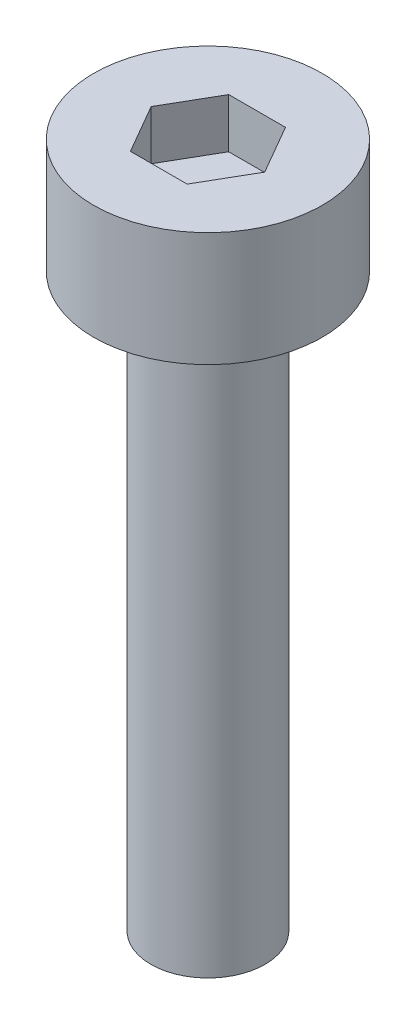
SolidWorks part; units mm, degrees
ref_plane "Front Plane" through (0, 0, 0) normal (0, 0, 1) x (1, 0, 0)
ref_plane "Top Plane" through (0, 0, 0) normal (0, 1, 0) x (1, 0, 0)
ref_plane "Right Plane" through (0, 0, 0) normal (1, 0, 0) x (0, 0, -1)
sketch "Sketch1" plane through (0, 0, 0) normal (0, 1, 0) x (1, 0, 0)
  circle A0 centre (0, 0) radius 1.5
  dimension "D1" = 3
extrude "ScrewShaft" add sketch "Sketch1" along normal blind 15
sketch "Sketch2" plane through (0, 15, 0) normal (0, 1, 0) x (1, 0, 0)
  circle A0 centre (0, 0) radius 3
  dimension "D1" = 6
extrude "Boss-Extrude2" add sketch "Sketch2" along normal blind 3
sketch "Sketch3" plane through (0, 18, 0) normal (0, 1, 0) x (1, 0, 0)
  line L0 (0, 0) -> (0, 1.29) construction
  line L1 (1.4896, 0) -> (0.7448, 1.29)
  line L2 (0.7448, 1.29) -> (-0.7448, 1.29)
  line L3 (-0.7448, 1.29) -> (-1.4896, 0)
  line L4 (-1.4896, 0) -> (-0.7448, -1.29)
  line L5 (-0.7448, -1.29) -> (0.7448, -1.29)
  line L6 (0.7448, -1.29) -> (1.4896, 0)
  circle A0 centre (0, 0) radius 1.29 construction
  dimension "D1" = 2.58
extrude "Cut-Extrude1" cut sketch "Sketch3" against normal blind 1.3
equation "\"X-ROD-SPACING\"=45"
equation "\"Y-ROD-SPACING\"=75"
equation "\"Z-ROD-SPACING\"=17.5"
equation "\"Y-BED-OFFSET\"=2"
equation "\"Y-BED-ROD-INSET\"=3.5"
equation "\"T-SLOT-NUT-FILLET-RADIUS\"=0.5"
equation "\"T-SLOT-SCREW-SHAFT-RADIUS\"=1.55"
equation "\"T-SLOT-SCREW-SHAFT-CUTOUT-LENGTH\"=11"
equation "\"T-SLOT-NUT-DEPTH\"=3.5"
equation "\"T-SLOT-NUT-WIDTH\"=2.85"
equation "\"T-SLOT-NUT-END-DISTANCE\"=8"
equation "\"ACRYLIC-THICKNESS\"=10"
equation "\"ACRYLIC-THICKNESS2\"=4.5"
equation "\"ACRYLIC-TAB-CUTOUT-SIZE\"=\"ACRYLIC-THICKNESS\"+\"ACRYLIC-TAB-TOLERANCE\"*2"
equation "\"ACRYLIC-TAB-WIDTH\"=\"ACRYLIC-THICKNESS\""
equation "\"ACRYLIC-M3-HOLE\"=2.9"
equation "\"SMOOTHROD-CAP-SCREW-DISTANCE\"=20"
equation "\"FRAME-WIDTH-INNER\"=370"
equation "\"NEMA17-HOLE-SPACING\"=31"
equation "\"NEMA17-CENTRAL-CUTOUT\"=22.5"
equation "\"Z-BRACKET-REACH\"=57"
equation "\"TOP-BRACKET-SPACING\"=40"
equation "\"SMOOTHROD-X-LENGTH\"=350"
equation "\"SMOOTHROD-Y-LENGTH\"=350"
equation "\"SMOOTHROD-Z-LENGTH\"=350"
equation "\"SMOOTHROD-TIGHTENING-HEADROOM\"=.25"
equation "\"LEADSCREW-Z-LENGTH\"=300"
equation "\"SCREW-LENGTH-FRAME\"=\"ACRYLIC-THICKNESS\" + 10"
equation "\"SCREW-HEAD-RADIUS\"=6"
equation "\"PRINTED-X-SMOOTHROD-DIAMETER\"=8.8"
equation "\"PRINTED-X-SMOOTHROD-CUTOUT\"=10"
equation "\"PRINTED-X-BASE-HEIGHT\"=10"
equation "\"PRINTED-LM8UU-CUTOUT-SIZE\"=15.5"
equation "\"PRINTED-LM8UU-CUTOUT-LENGTH\"=24.5"
equation "\"PRINTED-X-IDLER-HEIGHT\"=16"
equation "\"PSU-MOUNTING-WIDTH\"=50"
equation "\"PSU-MOUNTING-HEIGHT\"=150"
equation "\"D1@ScrewShaft\"=\"SCREW-LENGTH-MOTOR\""
equation "\"D1@Sketch2\"=\"SCREW-HEAD-RADIUS\""
equation "\"Y-BED-SCREW-SPACING\"=209"
equation "\"Y-BED-SCREW-CUTOUT-SLOT-HEIGHT\"=2.5"
equation "\"Z-ROD-INSET\"=13.5"
equation "\"SCREW-LENGTH-MOTOR\"=\"ACRYLIC-THICKNESS\" + 5"
equation "\"Y-BELT-TO-ROD-DISTANCE\"=20"
equation "\"SPOOL-HOLDER-ROD-SPACING\"=150"
